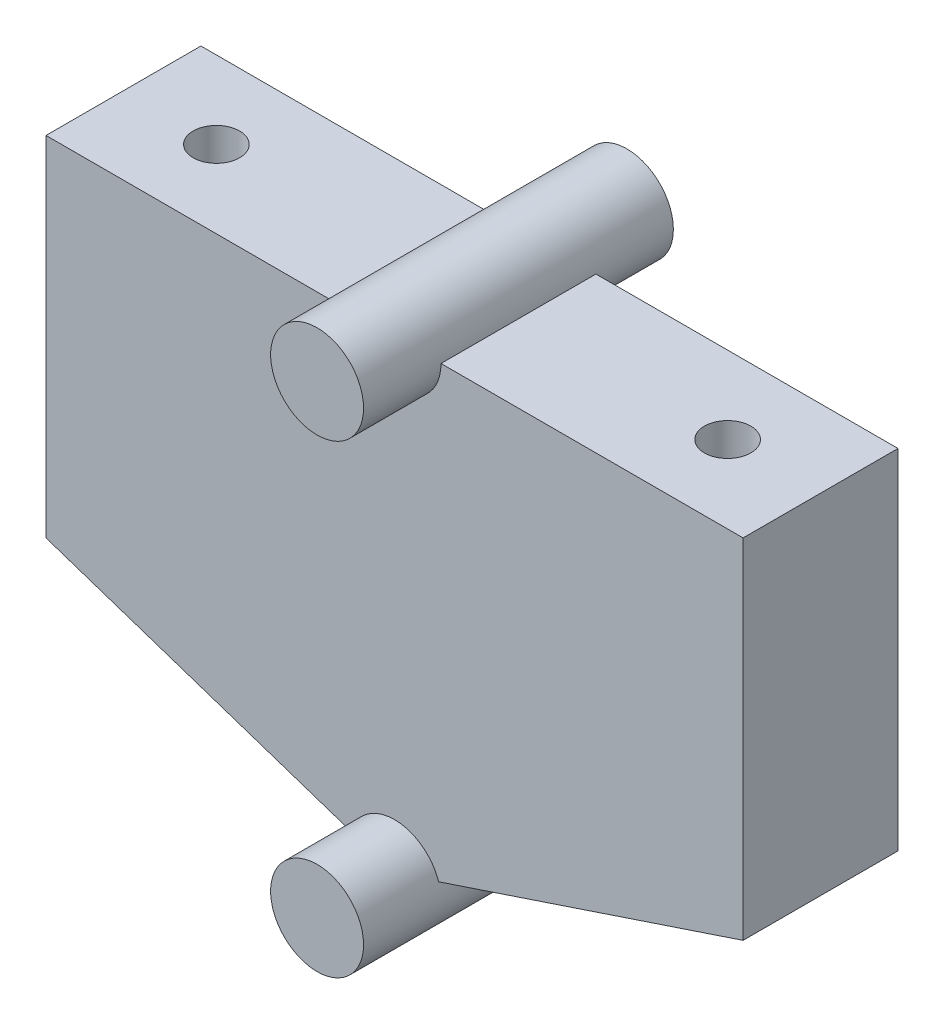
SolidWorks part; units mm, degrees
ref_plane "Front Plane" through (0, 0, 0) normal (0, 0, 1) x (1, 0, 0)
ref_plane "Top Plane" through (0, 0, 0) normal (0, 1, 0) x (1, 0, 0)
ref_plane "Right Plane" through (0, 0, 0) normal (1, 0, 0) x (0, 0, -1)
sketch "Sketch1" plane through (0, 0, 0) normal (0, 0, 1) x (1, 0, 0)
  line L0 (0, -18.75) -> (22.5, -11.25)
  line L1 (-22.5, 11.25) -> (22.5, 11.25)
  line L2 (-22.5, 11.25) -> (-22.5, -11.25)
  line L4 (22.5, 11.25) -> (22.5, -11.25)
  line L5 (-22.5, 11.25) -> (22.5, -11.25) construction
  line L6 (-22.5, -11.25) -> (22.5, 11.25) construction
  line L7 (-22.5, -11.25) -> (0, -18.75)
  circle A0 centre (0, -18.75) radius 3
  point P0 (0, 0)
  dimension "D4" = 6
  dimension "D1" = 22.5
  dimension "D2" = 30
  dimension "D3" = 45
extrude "Boss-Extrude1" add sketch "Sketch1" along normal blind 10 contours A0 L0 L4 L1 L2 L7 region at (0, -1.8176, 0)
extrude "Boss-Extrude2" add sketch "Sketch1<3>" along normal blind 15 and the other way blind 5 separate body contours L7 A0 L0 | L0 A0 L7 region at (0, -17.2309, 0) region at (0, -19.7525, 0)
sketch "Sketch1<3>" plane through (0, 0, 0) normal (0, 0, 1) x (1, 0, 0) same geometry as "Sketch1"
sketch "Sketch2" plane through (0, 11.25, 0) normal (0, 1, 0) x (1, 0, 0)
  line L0 (-22.5, -10) -> (-22.5, 0) construction
  line L2 (-22.5, -10) -> (22.5, -10) construction
  line L3 (0, -55) -> (0, 55) construction
  circle A0 centre (-16.5, -5) radius 1.5
  circle A2 centre (16.5, -5) radius 1.5
  dimension "D1" = 3
  dimension "D2" = 6
  dimension "5" = 5
extrude "Cut-Extrude1" cut sketch "Sketch2" against normal through all
sketch "Sketch3" plane through (0, 0, 10) normal (0, 0, 1) x (1, 0, 0)
  line L0 (-22.5, 11.25) -> (22.5, 11.25) construction
  circle A0 centre (0, 11.25) radius 3
  dimension "D1" = 6
extrude "Boss-Extrude3" add sketch "Sketch3" along normal blind 5 and the other way blind 15
